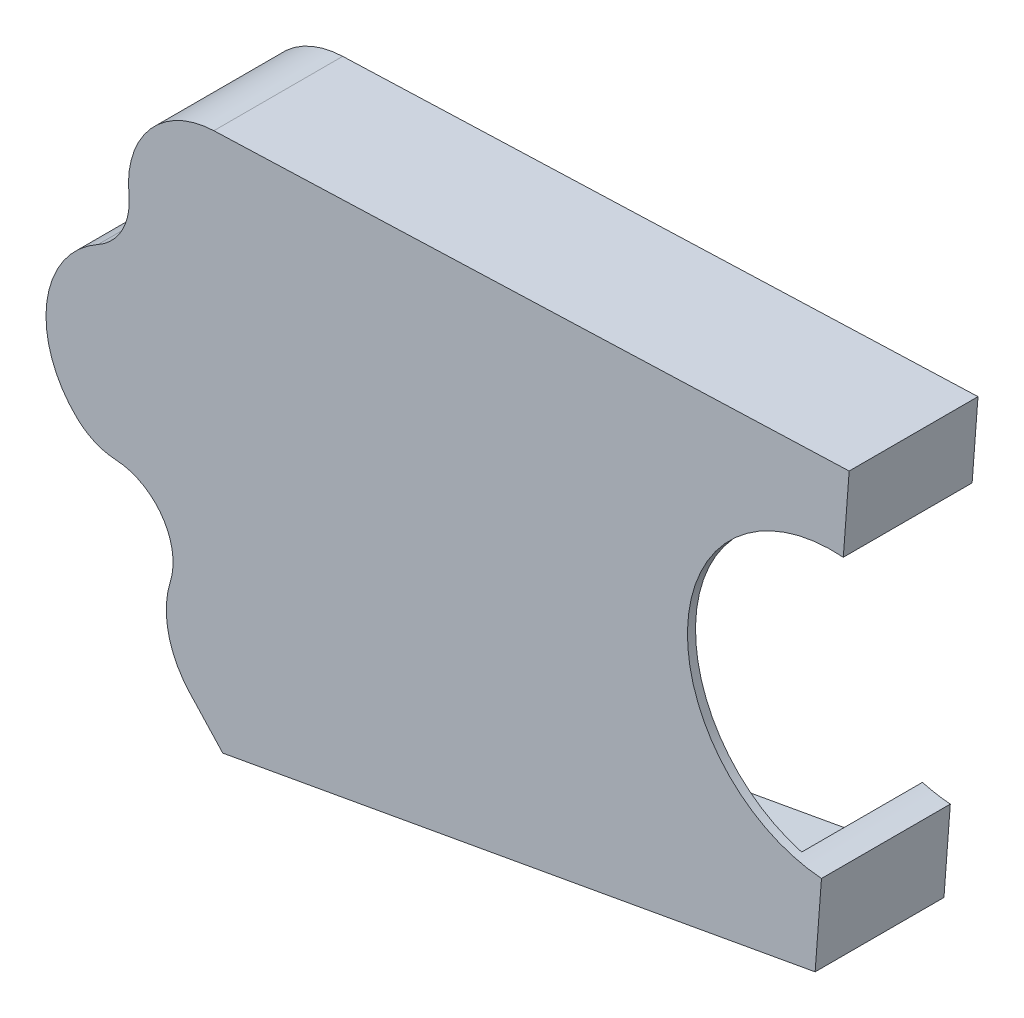
SolidWorks part; units mm, degrees
ref_plane "Front Plane" through (0, 0, 0) normal (0, 0, 1) x (1, 0, 0)
ref_plane "Top Plane" through (0, 0, 0) normal (0, 1, 0) x (1, 0, 0)
ref_plane "Right Plane" through (0, 0, 0) normal (1, 0, 0) x (0, 0, -1)
sketch "Sketch1" plane through (0, 0, 0) normal (0, 0, 1) x (1, 0, 0)
  line L8 (-119.5948, -74.4106) -> (-92.5405, -103.7404)
  line L9 (-119.5948, -74.4106) -> (-92.5405, -103.7404)
  line L10 (-71.3446, -104.5958) -> (-37.2211, -73.1197)
  line L11 (-71.3446, -104.5958) -> (-37.2211, -73.1197)
  line L16 (-27.1401, -68.1042) -> (68.9251, -50.7959)
  line L17 (-111.4072, -83.2869) -> (68.9251, -50.7959)
  line L18 (56.0883, 55.6165) -> (-113.6124, 49.4857)
  line L19 (56.0883, 55.6165) -> (-113.6124, 49.4857)
  line L20 (-114.4495, -69.6645) -> (-87.3952, -98.9943)
  line L21 (-114.4495, -69.6645) -> (-87.3952, -98.9943)
  line L22 (-76.0907, -99.4505) -> (-41.9673, -67.9744)
  line L23 (-76.0907, -99.4505) -> (-41.9673, -67.9744)
  line L28 (-28.3813, -61.2151) -> (67.6838, -43.9068)
  line L29 (-108.8671, -75.7165) -> (67.6838, -43.9068)
  line L30 (56.341, 48.621) -> (-113.3597, 42.4902)
  line L31 (56.341, 48.621) -> (-113.3597, 42.4902)
  line L32 (44.1846, 55.1864) -> (35.7309, -56.7765)
  line L33 (-27.1401, -68.1042) -> (68.9251, -50.7959) construction
  line L34 (-113.6124, 49.4857) -> (56.0883, 55.6165) construction
  line L35 (-111.6252, 43.3) -> (42.409, 31.6699) construction
  line L36 (36.6151, 47.9084) -> (29.1586, -50.848)
  arc A22 (-124.4228, -52.9336) -> (-137.9704, -33.4802) centre (-138.7403, -48.4604) ccw
  arc A23 (-124.4228, -52.9336) -> (-137.9704, -33.4802) centre (-138.7403, -48.4604) ccw
  arc A24 (-124.4228, -52.9336) -> (-119.5948, -74.4106) centre (-103.4238, -59.4942) ccw
  arc A25 (-124.4228, -52.9336) -> (-119.5948, -74.4106) centre (-103.4238, -59.4942) ccw
  arc A26 (-92.5405, -103.7404) -> (-71.3446, -104.5958) centre (-81.5148, -93.5701) ccw
  arc A27 (-92.5405, -103.7404) -> (-71.3446, -104.5958) centre (-81.5148, -93.5701) ccw
  arc A28 (-27.1401, -68.1042) -> (-37.2211, -73.1197) centre (-23.5699, -87.9191) ccw
  arc A29 (-27.1401, -68.1042) -> (-37.2211, -73.1197) centre (-23.5699, -87.9191) ccw
  arc A30 (68.9251, -50.7959) -> (91, -33.5) centre (63.6055, -21.2712) ccw
  arc A31 (68.9251, -50.7959) -> (91, -33.5) centre (63.6055, -21.2712) ccw
  arc A32 (91, -33.5) -> (80.2612, 44.7896) centre (22.6589, -2.9929) ccw
  arc A44 (91, -33.5) -> (80.2612, 44.7896) centre (22.6589, -2.9929) ccw
  arc A45 (80.2612, 44.7896) -> (56.0883, 55.6165) centre (57.1714, 25.636) ccw
  arc A46 (80.2612, 44.7896) -> (56.0883, 55.6165) centre (57.1714, 25.636) ccw
  arc A47 (-113.6124, 49.4857) -> (-134.7058, 25.2795) centre (-112.8181, 27.5) ccw
  arc A48 (-113.6124, 49.4857) -> (-134.7058, 25.2795) centre (-112.8181, 27.5) ccw
  arc A49 (-142.3827, 10.6321) -> (-134.7058, 25.2795) centre (-149.6292, 23.7656) ccw
  arc A50 (-142.3827, 10.6321) -> (-134.7058, 25.2795) centre (-149.6292, 23.7656) ccw
  arc A51 (-142.3827, 10.6321) -> (-147.5429, -29.3643) centre (-130.3054, -11.2571) ccw
  arc A52 (-142.3827, 10.6321) -> (-147.5429, -29.3643) centre (-130.3054, -11.2571) ccw
  arc A53 (-147.5429, -29.3643) -> (-137.9704, -33.4802) centre (-137.2004, -18.5) ccw
  arc A54 (-147.5429, -29.3643) -> (-137.9704, -33.4802) centre (-137.2004, -18.5) ccw
  arc A55 (-117.7413, -55.0211) -> (-137.611, -26.4895) centre (-138.7403, -48.4604) ccw
  arc A56 (-117.7413, -55.0211) -> (-137.611, -26.4895) centre (-138.7403, -48.4604) ccw
  arc A57 (-117.7413, -55.0211) -> (-114.4495, -69.6645) centre (-103.4238, -59.4942) ccw
  arc A58 (-117.7413, -55.0211) -> (-114.4495, -69.6645) centre (-103.4238, -59.4942) ccw
  arc A59 (-87.3952, -98.9943) -> (-76.0907, -99.4505) centre (-81.5148, -93.5701) ccw
  arc A60 (-87.3952, -98.9943) -> (-76.0907, -99.4505) centre (-81.5148, -93.5701) ccw
  arc A61 (-28.3813, -61.2151) -> (-41.9673, -67.9744) centre (-23.5699, -87.9191) ccw
  arc A62 (-28.3813, -61.2151) -> (-41.9673, -67.9744) centre (-23.5699, -87.9191) ccw
  arc A63 (67.6838, -43.9068) -> (84.608, -30.6466) centre (63.6055, -21.2712) ccw
  arc A73 (67.6838, -43.9068) -> (84.608, -30.6466) centre (63.6055, -21.2712) ccw
  arc A74 (84.608, -30.6466) -> (74.8736, 40.3204) centre (22.6589, -2.9929) ccw
  arc A75 (84.608, -30.6466) -> (74.8736, 40.3204) centre (22.6589, -2.9929) ccw
  arc A76 (74.8736, 40.3204) -> (56.341, 48.621) centre (57.1714, 25.636) ccw
  arc A77 (74.8736, 40.3204) -> (56.341, 48.621) centre (57.1714, 25.636) ccw
  arc A78 (-113.3597, 42.4902) -> (-127.7415, 25.986) centre (-112.8181, 27.5) ccw
  arc A79 (-113.3597, 42.4902) -> (-127.7415, 25.986) centre (-112.8181, 27.5) ccw
  arc A80 (-139.0011, 4.5031) -> (-127.7415, 25.986) centre (-149.6292, 23.7656) ccw
  arc A81 (-139.0011, 4.5031) -> (-127.7415, 25.986) centre (-149.6292, 23.7656) ccw
  arc A82 (-139.0011, 4.5031) -> (-142.7164, -24.2943) centre (-130.3054, -11.2571) ccw
  arc A83 (-139.0011, 4.5031) -> (-142.7164, -24.2943) centre (-130.3054, -11.2571) ccw
  arc A84 (-142.7164, -24.2943) -> (-137.611, -26.4895) centre (-137.2004, -18.5) ccw
  arc A85 (-142.7164, -24.2943) -> (-137.611, -26.4895) centre (-137.2004, -18.5) ccw
  circle A86 centre (40.0178, 0) radius 36
  arc A87 (30.3421, 33.636) -> (5.9163, 7.8798) centre (40.0178, 0) ccw construction
  dimension "D4" = 1
  dimension "D3" = 7
  dimension "D1" = 0
  dimension "D2" = 7
extrude "Boss-Extrude1" add sketch "Sketch1" along normal blind 30 contours A52 A54 A23 A25 L9 A27 L11 A29 L17 A31 A44 A46 L19 A48 A50 A85 A83 A81 A79 L31 A77 A75 A73 L29 A62 L23 A60 L21 A58 A56 | A62 L29 L21 L17 L23 | L29 A62 L23 L17 L32 | A86 L36 L29 L32 | A86 L32 L31 L36 region at (-122.5189, -63.7868, 0) region at (-72.9993, -72.6407, 0) region at (-2.1687, -60.1476, 0) region at (33.1772, -42.8072, 0) region at (39.6825, 41.9847, 0)
sketch "Sketch3" plane through (0, 0, 30) normal (0, 0, 1) x (1, 0, 0)
  line L0 (-65.2656, 44.2277) -> (121.4688, -34.2162)
  line L1 (-113.3597, 42.4902) -> (36.6151, 47.9084) construction
  line L2 (29.1586, -50.848) -> (-108.8671, -75.7165) construction
  dimension "D1" = 33
sketch "Sketch4" plane through (0, 0, 30) normal (0, 0, 1) x (1, 0, 0)
  line L21 (-113.3597, 42.4902) -> (36.6151, 47.9084)
  line L22 (36.6151, 47.9084) -> (35.6963, 35.7397)
  line L23 (42.7282, 35.8978) -> (44.1846, 55.1864)
  line L24 (44.1846, 55.1864) -> (-113.6124, 49.4857)
  line L25 (-119.5948, -74.4106) -> (-111.4072, -83.2869)
  line L26 (-111.4072, -83.2869) -> (35.7309, -56.7765)
  line L27 (35.7309, -56.7765) -> (37.3074, -35.8978)
  line L28 (30.379, -34.6856) -> (29.1586, -50.848)
  line L29 (29.1586, -50.848) -> (-108.8671, -75.7165)
  line L30 (-108.8671, -75.7165) -> (-114.4495, -69.6645)
  line L31 (-113.3597, 42.4902) -> (36.6151, 47.9084)
  line L32 (36.6151, 47.9084) -> (35.6963, 35.7397)
  line L33 (42.7282, 35.8978) -> (44.1846, 55.1864)
  line L34 (44.1846, 55.1864) -> (-113.6124, 49.4857)
  line L35 (-119.5948, -74.4106) -> (-111.4072, -83.2869)
  line L36 (-111.4072, -83.2869) -> (35.7309, -56.7765)
  line L37 (35.7309, -56.7765) -> (37.3074, -35.8978)
  line L38 (30.379, -34.6856) -> (29.1586, -50.848)
  line L39 (29.1586, -50.848) -> (-108.8671, -75.7165)
  line L40 (-108.8671, -75.7165) -> (-114.4495, -69.6645)
  circle A14 centre (40.0178, 0) radius 36
  arc A28 (-142.7164, -24.2943) -> (-137.611, -26.4895) centre (-137.2004, -18.5) ccw
  arc A29 (-139.0011, 4.5031) -> (-142.7164, -24.2943) centre (-130.3054, -11.2571) ccw
  arc A30 (-139.0011, 4.5031) -> (-127.7415, 25.986) centre (-149.6292, 23.7656) ccw
  arc A31 (-113.3597, 42.4902) -> (-127.7415, 25.986) centre (-112.8181, 27.5) ccw
  arc A32 (42.7282, 35.8978) -> (35.6963, 35.7397) centre (40.0178, 0) ccw
  arc A33 (-113.6124, 49.4857) -> (-134.7058, 25.2795) centre (-112.8181, 27.5) ccw
  arc A34 (-142.3827, 10.6321) -> (-134.7058, 25.2795) centre (-149.6292, 23.7656) ccw
  arc A35 (-142.3827, 10.6321) -> (-147.5429, -29.3643) centre (-130.3054, -11.2571) ccw
  arc A36 (-147.5429, -29.3643) -> (-137.9704, -33.4802) centre (-137.2004, -18.5) ccw
  arc A37 (-124.4228, -52.9336) -> (-137.9704, -33.4802) centre (-138.7403, -48.4604) ccw
  arc A38 (-124.4228, -52.9336) -> (-119.5948, -74.4106) centre (-103.4238, -59.4942) ccw
  arc A39 (30.379, -34.6856) -> (37.3074, -35.8978) centre (40.0178, 0) ccw
  arc A40 (-117.7413, -55.0211) -> (-114.4495, -69.6645) centre (-103.4238, -59.4942) ccw
  arc A41 (-117.7413, -55.0211) -> (-137.611, -26.4895) centre (-138.7403, -48.4604) ccw
  arc A42 (-142.7164, -24.2943) -> (-137.611, -26.4895) centre (-137.2004, -18.5) ccw
  arc A43 (-139.0011, 4.5031) -> (-142.7164, -24.2943) centre (-130.3054, -11.2571) ccw
  arc A44 (-139.0011, 4.5031) -> (-127.7415, 25.986) centre (-149.6292, 23.7656) ccw
  arc A45 (-113.3597, 42.4902) -> (-127.7415, 25.986) centre (-112.8181, 27.5) ccw
  arc A46 (42.7282, 35.8978) -> (35.6963, 35.7397) centre (40.0178, 0) ccw
  arc A47 (-113.6124, 49.4857) -> (-134.7058, 25.2795) centre (-112.8181, 27.5) ccw
  arc A48 (-142.3827, 10.6321) -> (-134.7058, 25.2795) centre (-149.6292, 23.7656) ccw
  arc A49 (-142.3827, 10.6321) -> (-147.5429, -29.3643) centre (-130.3054, -11.2571) ccw
  arc A50 (-147.5429, -29.3643) -> (-137.9704, -33.4802) centre (-137.2004, -18.5) ccw
  arc A51 (-124.4228, -52.9336) -> (-137.9704, -33.4802) centre (-138.7403, -48.4604) ccw
  arc A52 (-124.4228, -52.9336) -> (-119.5948, -74.4106) centre (-103.4238, -59.4942) ccw
  arc A53 (30.379, -34.6856) -> (37.3074, -35.8978) centre (40.0178, 0) ccw
  arc A54 (-117.7413, -55.0211) -> (-114.4495, -69.6645) centre (-103.4238, -59.4942) ccw
  arc A55 (-117.7413, -55.0211) -> (-137.611, -26.4895) centre (-138.7403, -48.4604) ccw
  arc M25 (-137.611, -26.4895) -> (-142.7164, -24.2943) centre (-137.2004, -18.5) cw
  arc M26 (-142.7164, -24.2943) -> (-139.0011, 4.5031) centre (-130.3054, -11.2571) cw
  arc M27 (-139.0011, 4.5031) -> (-127.7415, 25.986) centre (-149.6292, 23.7656) ccw
  arc M28 (-127.7415, 25.986) -> (-113.3597, 42.4902) centre (-112.8181, 27.5) cw
  line M29 (-113.3597, 42.4902) -> (36.6151, 47.9084)
  line M30 (36.6151, 47.9084) -> (35.6963, 35.7397)
  arc M31 (35.6963, 35.7397) -> (42.7282, 35.8978) centre (40.0178, 0) cw
  line M32 (42.7282, 35.8978) -> (44.1846, 55.1864)
  line M33 (44.1846, 55.1864) -> (-113.6124, 49.4857)
  arc M34 (-113.6124, 49.4857) -> (-134.7058, 25.2795) centre (-112.8181, 27.5) ccw
  arc M35 (-134.7058, 25.2795) -> (-142.3827, 10.6321) centre (-149.6292, 23.7656) cw
  arc M36 (-142.3827, 10.6321) -> (-147.5429, -29.3643) centre (-130.3054, -11.2571) ccw
  arc M37 (-147.5429, -29.3643) -> (-137.9704, -33.4802) centre (-137.2004, -18.5) ccw
  arc M38 (-137.9704, -33.4802) -> (-124.4228, -52.9336) centre (-138.7403, -48.4604) cw
  arc M39 (-124.4228, -52.9336) -> (-119.5948, -74.4106) centre (-103.4238, -59.4942) ccw
  line M40 (-119.5948, -74.4106) -> (-111.4072, -83.2869)
  line M41 (-111.4072, -83.2869) -> (35.7309, -56.7765)
  line M42 (35.7309, -56.7765) -> (37.3074, -35.8978)
  arc M43 (37.3074, -35.8978) -> (30.379, -34.6856) centre (40.0178, 0) cw
  line M44 (30.379, -34.6856) -> (29.1586, -50.848)
  line M45 (29.1586, -50.848) -> (-108.8671, -75.7165)
  line M46 (-108.8671, -75.7165) -> (-114.4495, -69.6645)
  arc M47 (-114.4495, -69.6645) -> (-117.7413, -55.0211) centre (-103.4238, -59.4942) cw
  arc M48 (-117.7413, -55.0211) -> (-137.611, -26.4895) centre (-138.7403, -48.4604) ccw
  dimension "D1" = 0
extrude "Boss-Extrude2" add sketch "Sketch4" along normal blind 2 contours A14 M30 M29 M28 M27 M26 M25 M48 M47 M46 M45 M44 | M48 M25 M26 M27 M28 M29 M30 M31 M32 M33 M34 M35 M36 M37 M38 M39 M40 M41 M42 M43 M44 M45 M46 M47 region at (-125.9577, 38.9499, 30) region at (-57.9317, -9.5661, 30)
